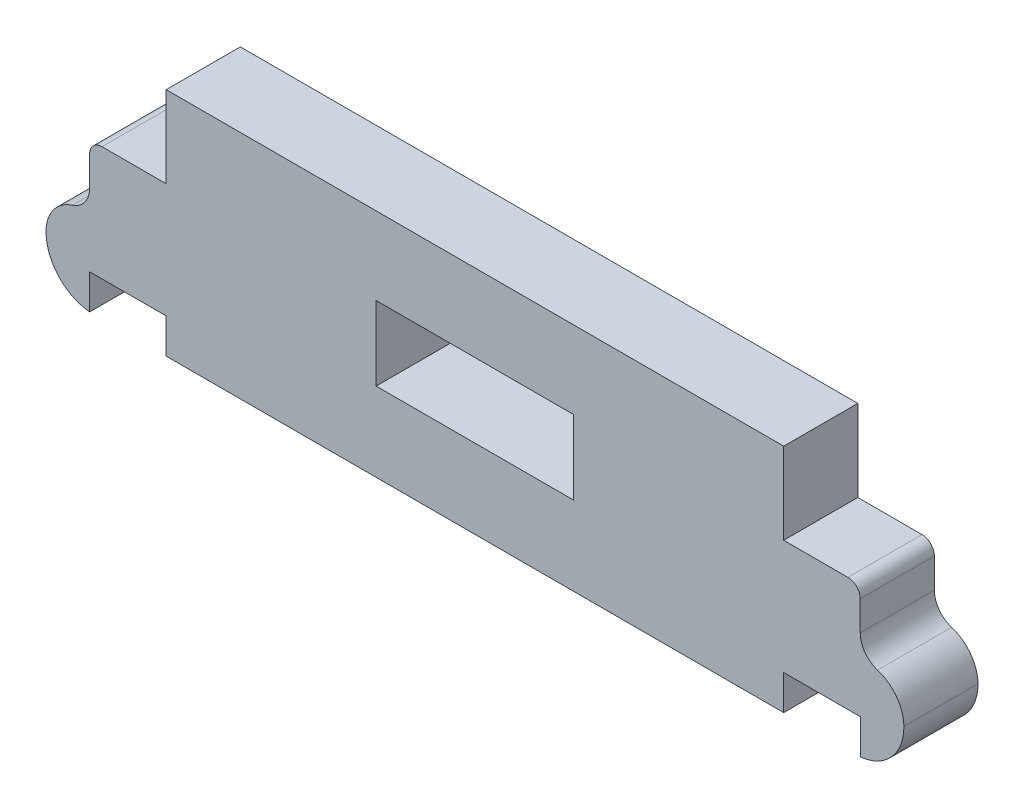
SolidWorks part; units mm, degrees
ref_plane "Plan de face" through (0, 0, 0) normal (0, 0, 1) x (1, 0, 0)
ref_plane "Plan de dessus" through (0, 0, 0) normal (0, 1, 0) x (1, 0, 0)
ref_plane "Plan de droite" through (0, 0, 0) normal (1, 0, 0) x (0, 0, -1)
sketch "Esquisse1" plane through (0, 0, 0) normal (0, 0, 1) x (1, 0, 0)
  line L0 (1141.2927, 1917.4046) -> (1141.2927, 1908.2046) construction
  line L1 (1127.9435, 1917.3065) -> (1152.9435, 1917.3065)
  line L2 (1152.9435, 1917.3065) -> (1152.9435, 1914.0065)
  line L3 (1152.9435, 1914.0065) -> (1155.5428, 1914.0065)
  line L4 (1156.0428, 1913.5065) -> (1156.0428, 1912.3091)
  line L5 (1140.4435, 1907.9628) -> (1140.4435, 1917.3065) construction
  line L6 (1156.0435, 1909.3714) -> (1156.0435, 1907.9628)
  line L7 (1156.0435, 1909.3714) -> (1152.9435, 1909.3714)
  line L8 (1152.9435, 1909.3714) -> (1152.9435, 1907.9628)
  line L9 (1152.9435, 1907.9628) -> (1127.9435, 1907.9628)
  line L10 (1127.9435, 1907.9628) -> (1127.9435, 1909.4559) construction
  line L11 (1127.9435, 1909.4559) -> (1124.555, 1909.4559) construction
  line L12 (1124.555, 1909.4559) -> (1124.555, 1907.9628) construction
  line L13 (1127.9435, 1909.3714) -> (1127.9435, 1907.9628)
  line L14 (1124.8435, 1909.3714) -> (1127.9435, 1909.3714)
  line L15 (1124.8435, 1909.3714) -> (1124.8435, 1907.9628)
  line L16 (1124.8443, 1913.5065) -> (1124.8443, 1912.3091)
  line L17 (1127.9435, 1914.0065) -> (1125.3443, 1914.0065)
  line L18 (1127.9435, 1917.3065) -> (1127.9435, 1914.0065)
  line L20 (1136.4435, 1914.1628) -> (1144.4435, 1914.1628)
  line L21 (1136.4435, 1914.1628) -> (1136.4435, 1911.1628)
  line L22 (1136.4435, 1911.1628) -> (1144.4435, 1911.1628)
  line L23 (1144.4435, 1914.1628) -> (1144.4435, 1911.1628)
  arc A0 (1156.7424, 1911.3553) -> (1157.8102, 1909.9104) centre (1156.2841, 1909.8996) cw
  arc A1 (1157.8102, 1909.9104) -> (1156.0435, 1907.9628) centre (1155.8685, 1909.8966) cw
  arc A2 (1123.0768, 1909.9104) -> (1124.8435, 1907.9628) centre (1125.0185, 1909.8966) ccw
  arc A3 (1124.1446, 1911.3553) -> (1123.0768, 1909.9104) centre (1124.6029, 1909.8996) ccw
  arc A4 (1156.0428, 1912.3091) -> (1156.7424, 1911.3553) centre (1157.0428, 1912.3091) ccw
  arc A5 (1124.1446, 1911.3553) -> (1124.8443, 1912.3091) centre (1123.8443, 1912.3091) ccw
  arc A6 (1155.5428, 1914.0065) -> (1156.0428, 1913.5065) centre (1155.5428, 1913.5065) cw
  arc A7 (1124.8443, 1913.5065) -> (1125.3443, 1914.0065) centre (1125.3443, 1913.5065) cw
  point P32 (1156.0428, 1911.4065)
  point P35 (1124.8443, 1911.4065)
  point P38 (1156.0428, 1914.0065)
  point P41 (1124.8443, 1914.0065)
  dimension "D6" = 3.1
  dimension "D8" = 1
  dimension "D9" = 0.5
  dimension "D1" = 9.2
  dimension "D2" = 25
  dimension "D3" = 3.3
  dimension "D4" = 3.0993
  dimension "D5" = 2.6
  dimension "D7" = 25
  dimension "D10" = 8
  dimension "D11" = 3
  dimension "D12" = 3.2
  dimension "D13" = 4
base flange "Tôle de base pliée1" sketch "Esquisse1" thickness 3 reverse thickness direction no parameters "D1"=1.5
sketch "Lignes de pliage1" [suppressed] plane through (0, 0, 0) normal (0, 1, 0) x (1, 0, 0)
sketch "Cube de visualisation1" [suppressed] plane through (0, 0, 0) normal (0, 1, 0) x (1, 0, 0)
sheet metal parameters "Tôlerie1" thickness 3 parameters "D1"=1.5
flat pattern "Etat déplié1" [suppressed]
sketch "Lignes de pliage2" plane through (0, 0, 0) normal (0, 1, 0) x (1, 0, 0)
sketch3d "Cube de visualisation2" [suppressed]
  line L0 (-2.2674, 3.8, 0) -> (32.4659, 3.8, 0) construction
  line L1 (-2.2674, -5.5437, 0) -> (32.4659, -5.5437, 0) construction
  line L2 (-2.2674, 3.8, 0) -> (-2.2674, -5.5437, 0) construction
  line L3 (32.4659, 3.8, 0) -> (32.4659, -5.5437, 0) construction
